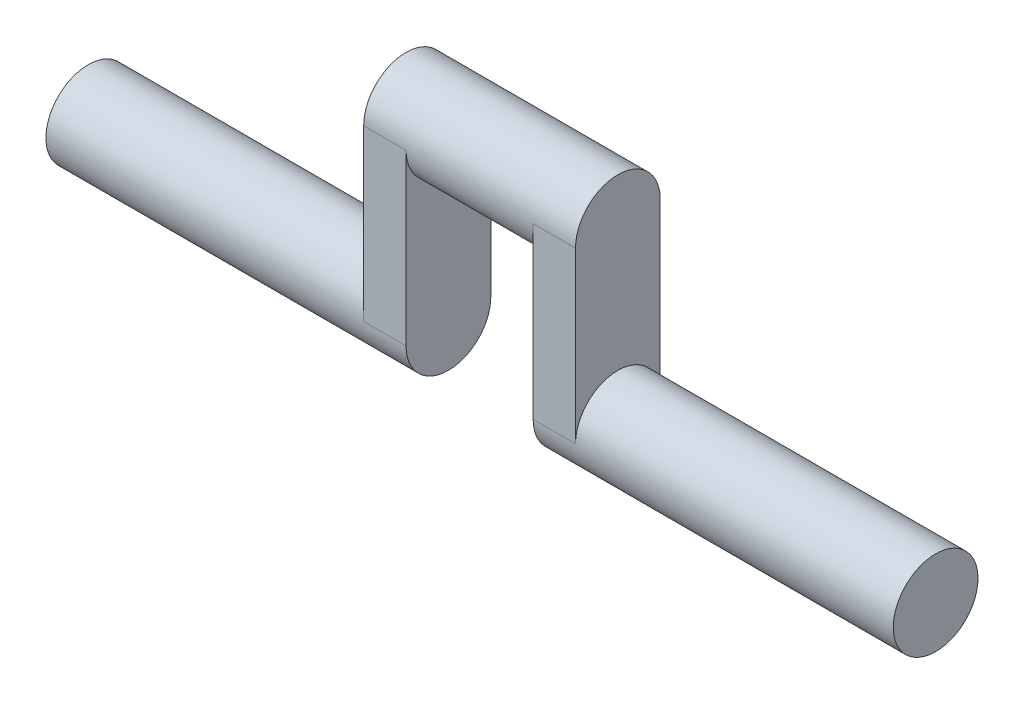
SolidWorks part; units mm, degrees
ref_plane "Front Plane" through (0, 0, 0) normal (0, 0, 1) x (1, 0, 0)
ref_plane "Top Plane" through (0, 0, 0) normal (0, 1, 0) x (1, 0, 0)
ref_plane "Right Plane" through (0, 0, 0) normal (1, 0, 0) x (0, 0, -1)
sketch "Sketch1" plane through (0, 0, 0) normal (1, 0, 0) x (0, 0, -1)
  line L0 (-5, 20) -> (-5, 0)
  line L1 (5, 20) -> (5, 0)
  circle A0 centre (0, 0) radius 5
  circle A1 centre (0, 20) radius 5
  dimension "D1" = 10
  dimension "D2" = 20
extrude "Boss-Extrude1" add sketch "Sketch1" against normal blind 42.5 contours A0 region at (0, 0, 0)
extrude "Boss-Extrude2" add sketch "Sketch1<3>" against normal blind 5 from offset 37.5 contours A1 L0 A0 L1 | A1 region at (0, 10, 0) region at (0, 20, 0) offset against normal yes
sketch "Sketch1<3>" plane through (0, 0, 0) normal (1, 0, 0) x (0, 0, -1) same geometry as "Sketch1"
extrude "Boss-Extrude3" add sketch "Sketch1<4>" against normal blind 25 from offset 37.5 contours A1 region at (0, 20, 0) offset against normal yes
sketch "Sketch1<4>" plane through (0, 0, 0) normal (1, 0, 0) x (0, 0, -1) same geometry as "Sketch1"
extrude "Boss-Extrude4" add sketch "Sketch1<5>" along normal blind 5 from surface contours A1 L0 A0 L1 region at (0, 10, 0) starting at face at (-62.5, 20, -5)
sketch "Sketch1<5>" plane through (0, 0, 0) normal (1, 0, 0) x (0, 0, -1) same geometry as "Sketch1"
extrude "Boss-Extrude5" add sketch "Sketch1<6>" against normal blind 42.5 from offset 57.5 contours A0 region at (0, 0, 0) offset against normal yes
sketch "Sketch1<6>" plane through (0, 0, 0) normal (1, 0, 0) x (0, 0, -1) same geometry as "Sketch1"
